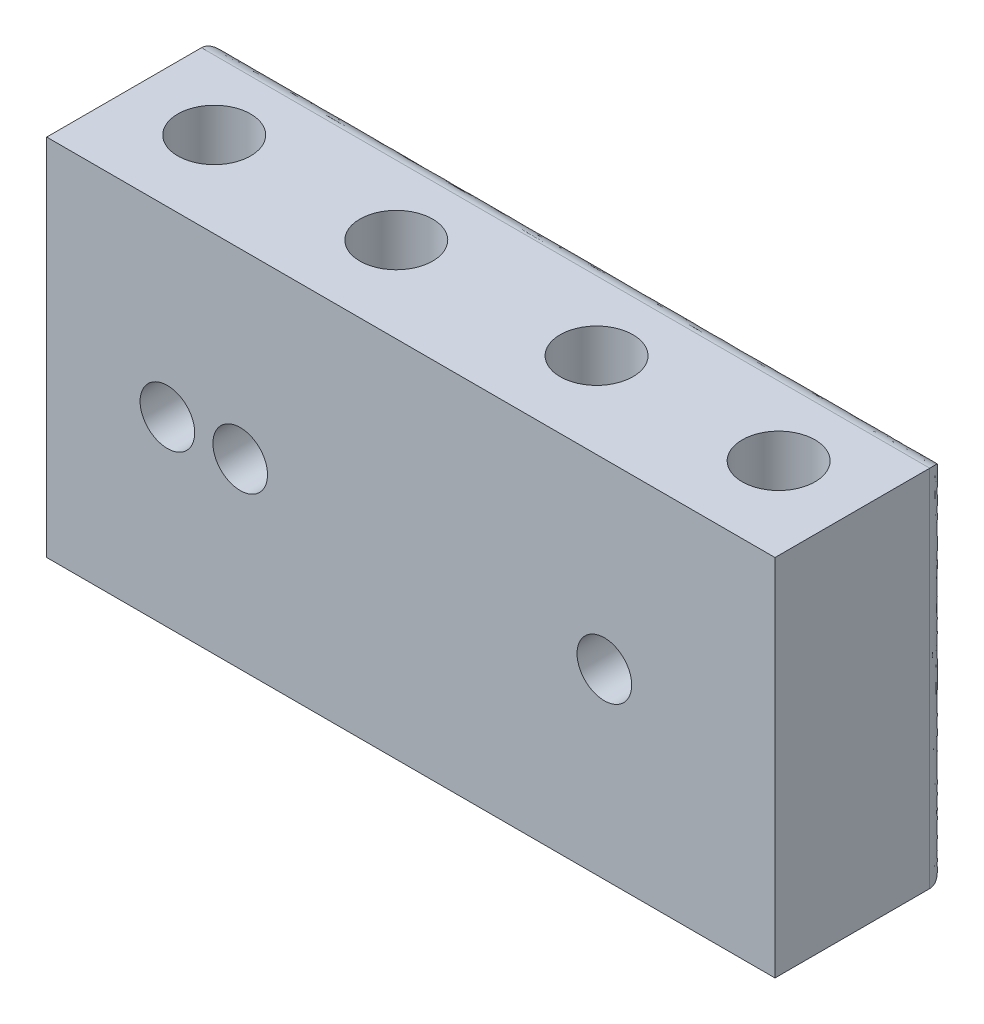
SolidWorks part; units mm, degrees
material "petg 20%"
ref_plane "Front Plane" through (0, 0, 0) normal (0, 0, 1) x (1, 0, 0)
ref_plane "Top Plane" through (0, 0, 0) normal (0, 1, 0) x (1, 0, 0)
ref_plane "Right Plane" through (0, 0, 0) normal (1, 0, 0) x (0, 0, -1)
sketch "Sketch1" plane through (0, 0, 0) normal (0, 0, 1) x (1, 0, 0)
  line L1 (20, 10) -> (-20, 10)
  line L2 (20, 10) -> (20, -10)
  line L3 (20, -10) -> (-20, -10)
  line L4 (-20, 10) -> (-20, -10)
  line L5 (20, 10) -> (-20, -10) construction
  line L6 (20, -10) -> (-20, 10) construction
  point P0 (0, 0)
  dimension "D1" = 40
  dimension "D2" = 20
extrude "Boss-Extrude1" add sketch "Sketch1" along normal blind 9.5
sketch "Sketch3" plane through (0, 0, 0) normal (0, 0, -1) x (-1, 0, 0)
  line L0 (13.3714, -3.45) -> (1.3714, -3.45)
  line L1 (13.3714, 3.45) -> (1.3714, 3.45)
  line L2 (-10.6286, 0) -> (9.9214, 0) construction
  arc A0 (-6.4266, 6.3327) -> (-6.4266, -6.3327) centre (-10.6286, 0) ccw
  arc A1 (13.3714, -3.45) -> (13.3714, 3.45) centre (13.3714, 0) ccw
  spline S0 degree 2 poles (-6.4266, -6.3327) (-3.0128, -3.5547) (1.3714, -3.45) knots 0 0 0 1 1 1
  spline S1 degree 2 poles (-6.4266, 6.3327) (-3.0128, 3.5547) (1.3714, 3.45) knots 0 0 0 1 1 1
  dimension "D1" = 15.2
  dimension "D2" = 6.9
extrude "Cut-Extrude1" cut sketch "Sketch3" against normal blind 2
fillet "Fillet1" radius 1 4 edges at (-20, 0, 0) (0, -10, 0) (0, 10, 0) (20, 0, 0) first distance on face at (-1.3801, -0.4805, 0)
sketch "Sketch4" plane through (0, 10, 0) normal (0, 1, 0) x (1, 0, 0)
  circle A0 centre (-15.5, -4.8) radius 2
  circle A1 centre (-5.5, -4.8) radius 2
  circle A2 centre (5.5, -4.8) radius 2
  circle A3 centre (15.5, -4.8) radius 2
  dimension "D1" = 4
  dimension "D2" = 4
extrude "Cut-Extrude2" cut sketch "Sketch4" against normal through all
sketch "Sketch5" plane through (0, 0, 0) normal (0, 0, -1) x (-1, 0, 0)
  circle A0 centre (13.3714, 0) radius 1.5
  circle A1 centre (9.3714, 0) radius 1.5
  circle A2 centre (-10.6286, 0) radius 1.5
  dimension "D1" = 3
  dimension "D2" = 3
  dimension "D3" = 4
  dimension "D4" = 3
extrude "Cut-Extrude3" cut sketch "Sketch5" against normal through all
